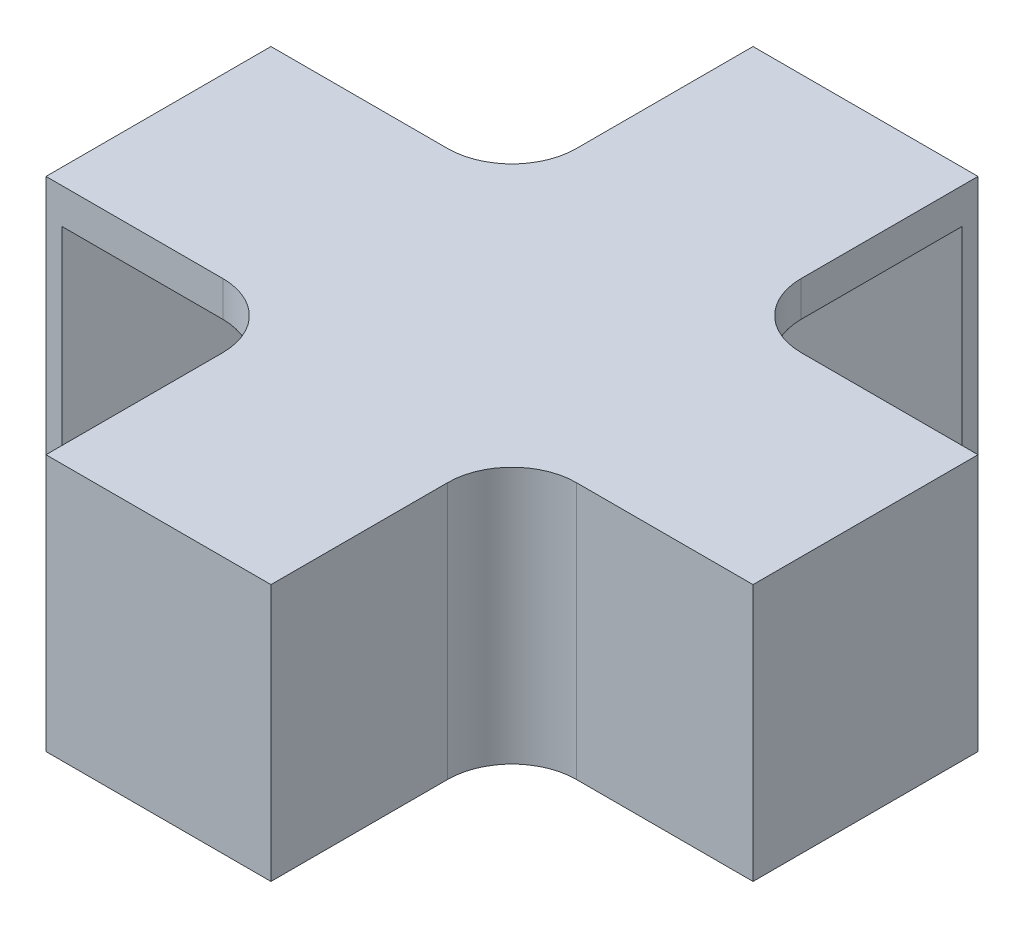
SolidWorks part; units mm, degrees
ref_plane "Front Plane" through (0, 0, 0) normal (0, 0, 1) x (1, 0, 0)
ref_plane "Top Plane" through (0, 0, 0) normal (0, 1, 0) x (1, 0, 0)
ref_plane "Right Plane" through (0, 0, 0) normal (1, 0, 0) x (0, 0, -1)
sketch "Sketch1" plane through (0, 0, 0) normal (0, 1, 0) x (1, 0, 0)
  line L0 (-70.1964, 67.8236) -> (-35.1964, 67.8236)
  line L1 (-35.1964, 67.8236) -> (-35.1964, 40.3236)
  line L2 (-35.1964, -42.1764) -> (-70.1964, -42.1764)
  line L3 (-70.1964, -42.1764) -> (-70.1964, -14.6764)
  line L4 (-70.1964, 67.8236) -> (-70.1964, 40.3236)
  line L5 (-80.1964, 30.3236) -> (-107.6964, 30.3236)
  line L6 (-107.6964, 30.3236) -> (-107.6964, -4.6764)
  line L7 (-107.6964, -4.6764) -> (-80.1964, -4.6764)
  line L8 (-25.1964, -4.6764) -> (2.3036, -4.6764)
  line L9 (2.3036, -4.6764) -> (2.3036, 30.3236)
  line L10 (2.3036, 30.3236) -> (-25.1964, 30.3236)
  line L11 (-35.1964, 67.8236) -> (-35.1964, 40.3236)
  line L12 (2.3036, -4.6764) -> (-25.1964, -4.6764)
  line L13 (-70.1964, -14.6764) -> (-70.1964, -42.1764)
  line L14 (-35.1964, -14.6764) -> (-35.1964, -42.1764)
  line L15 (-70.1964, 30.3236) -> (-70.1964, 30.3254)
  line L16 (-35.1964, -4.6764) -> (-35.1964, -4.6782)
  line L17 (-42.4433, 58.0785) -> (-35.1964, 65.3254)
  line L18 (-42.4433, 58.0785) -> (-7.4415, 23.0767)
  line L19 (-7.4415, 23.0767) -> (-0.1946, 30.3236)
  line L20 (-97.9512, 2.5706) -> (-62.9494, -32.4312)
  line L21 (-42.4433, 58.0785) -> (-105.1981, -4.6764)
  line L22 (-7.4415, 23.0767) -> (-70.1964, -39.6782)
  line L23 (-35.1964, -14.6764) -> (-35.1964, -42.1764)
  line L24 (-35.1946, -4.6764) -> (-35.1964, -4.6764)
  line L25 (-70.1964, 40.3236) -> (-70.1964, 67.8236)
  line L26 (-62.9494, -32.4312) -> (-70.1964, -39.6782)
  line L27 (-97.9512, 2.5706) -> (-105.1981, -4.6764)
  arc A0 (-70.1964, 40.3236) -> (-80.1964, 30.3236) centre (-80.1964, 40.3236) cw
  arc A1 (-25.1964, 30.3236) -> (-35.1964, 40.3236) centre (-25.1964, 40.3236) cw
  arc A2 (-25.1964, -4.6764) -> (-35.1964, -14.6764) centre (-25.1964, -14.6764) ccw
  arc A3 (-80.1964, -4.6764) -> (-70.1964, -14.6764) centre (-80.1964, -14.6764) cw
  point P13 (-70.1964, 30.3236)
  point P17 (-35.1964, 30.3236)
  point P23 (-70.1964, -4.6764)
  dimension "D6" = 10
  dimension "D7" = 10
  dimension "D8" = 10
  dimension "D9" = 10
  dimension "D1" = 35
  dimension "D2" = 110
  dimension "D3" = 35
  dimension "D4" = 37.5
  dimension "D5" = 37.5
  dimension "D11" = 78.5
  dimension "D12" = 49.5
extrude "Boss-Extrude6" add sketch "Sketch1" along normal blind 40 contours L4 A0 L5 L6 L7 L21 L17 L1 L0 | L20 L21 L7 | L7 A3 L13 L20 L22 L16 L24 L18 L10 A1 L1 L21 | A2 L8 L9 L10 L19 L22 L3 L2 L14 | L22 L20 L13 | L18 L19 L10 | L17 L18 L11 region at (-52.6964, 0, -66.7983) region at (-37.612, 0, -58.0785) region at (-52.6964, 0, -12.8236) region at (-7.4415, 0, -27.908) region at (1.0545, 0, -29.2983) region at (-97.9512, 0, 2.2607) region at (-67.7807, 0, 32.4312)
extrude "Cut-Extrude2" cut sketch "Sketch1<9>" along normal blind 34.5 contours L7 A3 L13 L20 L22 L16 L24 L18 L10 A1 L1 L21 | A1 L10 L18 L1 | A3 L7 L20 L13 | L17 L18 L11 | L20 L21 L7 | L22 L20 L13 | L18 L19 L10 region at (-37.612, 0, -58.0785) region at (-27.8373, 0, -37.6826) region at (-52.6964, 0, -12.8236) region at (-7.4415, 0, -27.908) region at (-97.9512, 0, 2.2607) region at (-77.5554, 0, 12.0354) region at (-67.7807, 0, 32.4312)
sketch "Sketch1<9>" plane through (0, 0, 0) normal (0, 1, 0) x (1, 0, 0) same geometry as "Sketch1"
